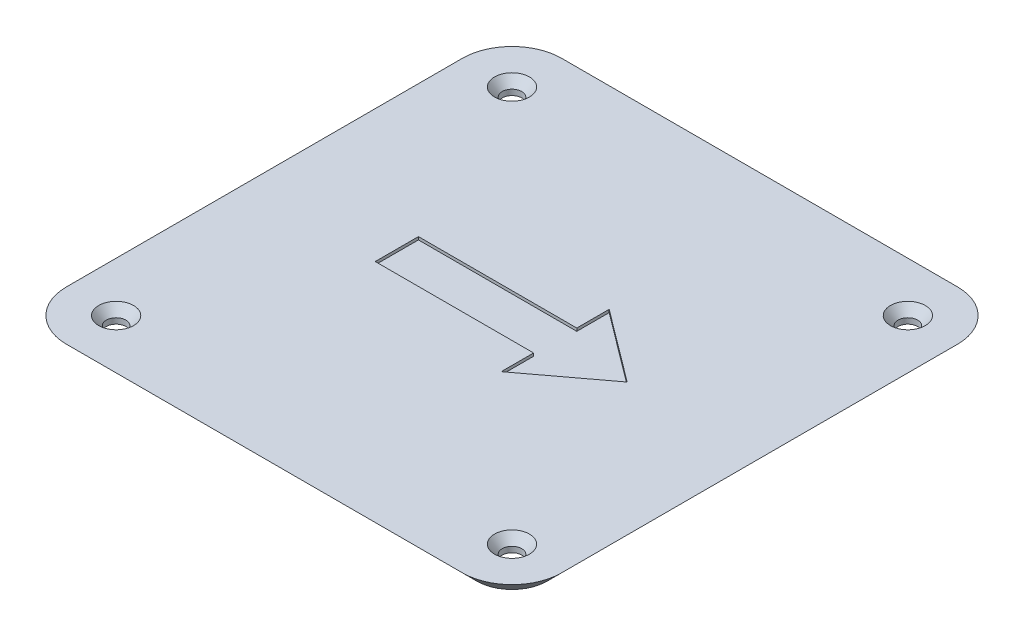
SolidWorks part; units mm, degrees
ref_plane "Plane XZ" through (0, 0, 0) normal (0, 0, 1) x (1, 0, 0)
ref_plane "Plane XY" through (0, 0, 0) normal (0, 1, 0) x (1, 0, 0)
ref_plane "Plane YZ" through (0, 0, 0) normal (1, 0, 0) x (0, 0, -1)
sketch "Sketch1" plane through (0, 0, 0) normal (0, 1, 0) x (1, 0, 0)
  line L0 (-43.815, 0) -> (43.815, 0) construction
  line L1 (-34.925, 43.815) -> (34.925, 43.815) construction
  line L2 (-43.815, 34.925) -> (-43.815, -34.925) construction
  line L3 (-34.925, -43.815) -> (34.925, -43.815) construction
  line L4 (43.815, 34.925) -> (43.815, -34.925) construction
  line L9 (0, 0) -> (0, -43.815) construction
  line L10 (-43.688, 34.925) -> (-43.688, -34.925)
  line L11 (-34.925, -43.688) -> (34.925, -43.688)
  line L12 (43.688, 34.925) -> (43.688, -34.925)
  line L13 (-34.925, 43.688) -> (34.925, 43.688)
  arc A4 (-43.815, -34.925) -> (-34.925, -43.815) centre (-34.925, -34.925) ccw construction
  arc A5 (34.925, -43.815) -> (43.815, -34.925) centre (34.925, -34.925) ccw construction
  arc A6 (34.925, 43.815) -> (43.815, 34.925) centre (34.925, 34.925) cw construction
  arc A7 (-34.925, 43.815) -> (-43.815, 34.925) centre (-34.925, 34.925) ccw construction
  arc A8 (-43.688, -34.925) -> (-34.925, -43.688) centre (-34.925, -34.925) ccw
  arc A9 (34.925, -43.688) -> (43.688, -34.925) centre (34.925, -34.925) ccw
  arc A10 (34.925, 43.688) -> (43.688, 34.925) centre (34.925, 34.925) cw
  arc A11 (-34.925, 43.688) -> (-43.688, 34.925) centre (-34.925, 34.925) ccw
  point P24 (-43.815, -43.815)
  dimension "D7" = 8.89
  dimension "D1" = 87.63
  dimension "D2" = 87.63
  dimension "D3" = 0.127
extrude "Boss-Extrude1" add sketch "Sketch1" along normal blind 2.54
chamfer "Chamfer1" distance 2.54 angle 45 8 edges at (-43.688, 0, 0) (-41.1214, 0, 41.1214) (-41.1214, 0, -41.1214) (0, 0, 43.688) (0, 0, -43.688) (41.1214, 0, 41.1214) (41.1214, 0, -41.1214) (43.688, 0, 0)
hole_wizard "CSK for #4 Flat Head Machine Screw1" positions "Sketch4" profile "Sketch6" countersink size "#4" standard "ANSI Inch" end condition through all
sketch "Sketch4" plane through (0, 2.54, 0) normal (0, 1, 0) x (1, 0, 0)
  arc A0 (-43.688, -34.925) -> (-34.925, -43.688) centre (-34.925, -34.925) ccw construction
  arc A1 (34.925, -43.688) -> (43.688, -34.925) centre (34.925, -34.925) ccw construction
  arc A2 (43.688, 34.925) -> (34.925, 43.688) centre (34.925, 34.925) ccw construction
  arc A3 (-34.925, 43.688) -> (-43.688, 34.925) centre (-34.925, 34.925) ccw construction
  point P0 (-34.925, 34.925)
  point P3 (34.925, 34.925)
  point P6 (-34.925, -34.925)
  point P9 (34.925, -34.925)
sketch "Sketch6" plane through (-34.925, 2.54, -34.925) normal (1, 0, 0) x (0, 0, 1)
  line L0 (0, 0) -> (0, 2.54)
  line L1 (0, 2.54) -> (1.7272, 2.54)
  line L2 (1.7272, 2.54) -> (1.7272, 1.5543)
  line L3 (1.7272, 1.5543) -> (3.0783, 0)
  line L5 (3.0783, 0) -> (0, 0)
  line L6 (-1.7272, 1.5543) -> (-3.0783, 0) construction
  line L11 (0, -6.35) -> (0, 107.95) construction
  dimension "Thru Hole Dia." = 3.4544
  dimension "Thru Hole Depth" = 2.54
  dimension "Near C'Sink Dia." = 6.1566
  dimension "Near C'Sink Angle" = 82
sketch "Sketch3" plane through (0, 2.54, 0) normal (0, 1, 0) x (1, 0, 0)
  line L0 (0, 3.81) -> (7.62, 3.81)
  line L1 (7.62, 3.81) -> (7.62, 9.525)
  line L2 (7.62, 9.525) -> (20.32, 0)
  line L3 (20.32, 0) -> (7.62, -9.525)
  line L4 (7.62, -9.525) -> (7.62, -3.81)
  line L5 (7.62, -3.81) -> (0, -3.81)
  line L6 (0, -3.81) -> (0, 3.81) construction
  line L7 (0, 3.81) -> (-20.32, 3.81)
  line L8 (-20.32, 3.81) -> (-20.32, -3.81)
  line L9 (-20.32, -3.81) -> (0, -3.81)
  dimension "D1" = 7.62
  dimension "D2" = 7.62
  dimension "D3" = 19.05
  dimension "D4" = 12.7
  dimension "D5" = 20.32
extrude "Cut-Extrude2" cut sketch "Sketch3" against normal blind 0.508
